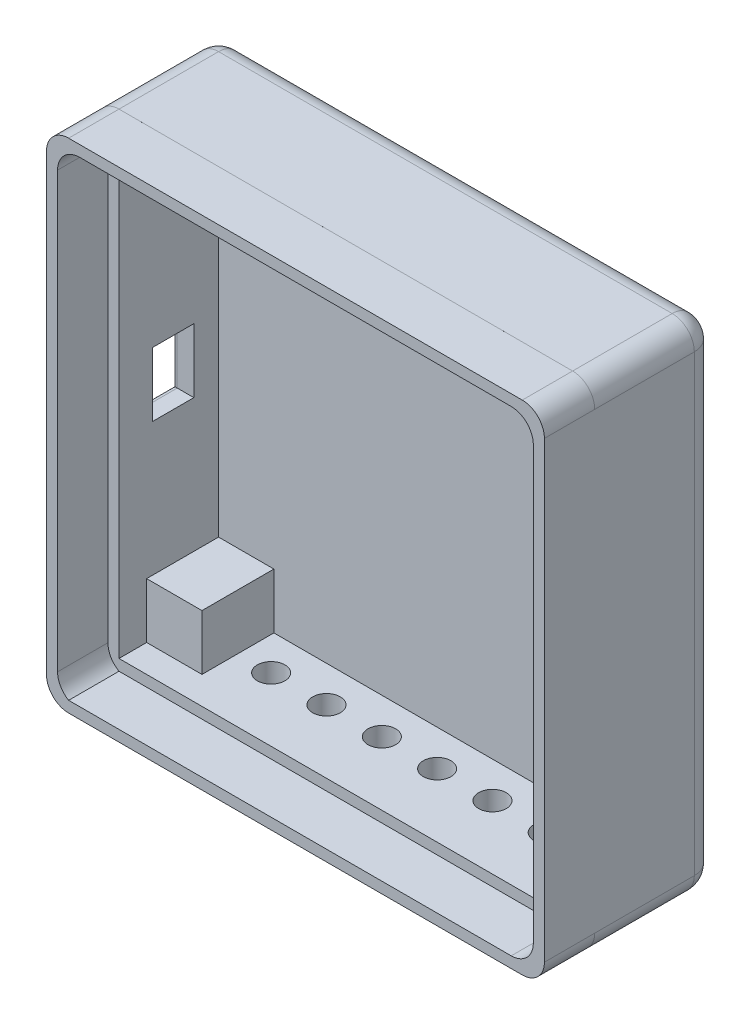
SolidWorks part; units mm, degrees
ref_plane "Piano frontale" through (0, 0, 0) normal (0, 0, 1) x (1, 0, 0)
ref_plane "Piano superiore" through (0, 0, 0) normal (0, 1, 0) x (1, 0, 0)
ref_plane "Piano destro" through (0, 0, 0) normal (1, 0, 0) x (0, 0, -1)
sketch "Schizzo2" plane through (0, 0, 0) normal (0, 0, 1) x (1, 0, 0)
  line L1 (0, 0) -> (45, 0)
  line L2 (0, 0) -> (0, 45)
  line L3 (0, 45) -> (45, 45)
  line L4 (45, 0) -> (45, 45)
  dimension "D1" = 45
  dimension "D2" = 45
extrude "Estrusione-Estrusione2" add sketch "Schizzo2" along normal blind 11
shell "Svuota1" thickness 2 removed face at (22.5, 22.5, 11)
fillet "Raccordo1" radius 2 4 edges at (45, 45, 5.5) (45, 0, 5.5) (0, 0, 5.5) (0, 45, 5.5)
fillet "Raccordo2" radius 2 8 edges at (44.4142, 0.5858, 0) (22.5, 0, 0) (0.5858, 0.5858, 0) (0, 22.5, 0) (0.5858, 44.4142, 0) (22.5, 45, 0) (44.4142, 44.4142, 0) (45, 22.5, 0)
sketch "Schizzo3" plane through (0, 0, 2) normal (0, 0, 1) x (1, 0, 0)
  line L0 (43, 43) -> (2, 43) construction
  line L1 (2, 43) -> (7, 43)
  line L2 (2, 43) -> (2, 38)
  line L3 (2, 38) -> (7, 38)
  line L4 (7, 43) -> (7, 38)
  line L5 (43, 43) -> (2, 43) construction
  dimension "D1" = 5
  dimension "D2" = 5
extrude "Estrusione-Estrusione3" add sketch "Schizzo3" along normal blind 6.5
sketch "Schizzo4" plane through (0, 0, 2) normal (0, 0, 1) x (1, 0, 0)
  line L1 (43, 2) -> (38, 2)
  line L2 (43, 2) -> (43, 7)
  line L3 (43, 7) -> (38, 7)
  line L4 (38, 2) -> (38, 7)
  dimension "D1" = 5
  dimension "D2" = 5
extrude "Estrusione-Estrusione4" add sketch "Schizzo4" along normal blind 6.5
fillet "Raccordo3" radius 4 2 edges at (38, 7, 5.25) (7, 38, 5.25)
sketch "Schizzo5" plane through (0, 0, 2) normal (0, 0, 1) x (1, 0, 0)
  line L0 (43, 2) -> (43, 43) construction
  line L1 (43, 43) -> (38, 43)
  line L2 (43, 43) -> (43, 38)
  line L3 (43, 38) -> (38, 38)
  line L4 (38, 43) -> (38, 38)
  line L5 (43, 43) -> (7, 43) construction
  line L7 (2, 2) -> (7, 2)
  line L8 (2, 2) -> (2, 7)
  line L9 (2, 7) -> (7, 7)
  line L10 (7, 2) -> (7, 7)
  dimension "D1" = 5
  dimension "D2" = 5
  dimension "D3" = 5
  dimension "D4" = 5
extrude "Estrusione-Estrusione5" add sketch "Schizzo5" along normal blind 6.5 contours L2 L1 L4 L3 | L8 L7 L10 L9
sketch "Schizzo7" plane through (0, 0, 0) normal (-1, 0, 0) x (0, 0, 1)
  line L1 (4.2347, 24.8244) -> (7.9559, 24.8244)
  line L2 (4.2347, 24.8244) -> (4.2347, 19.0329)
  line L3 (4.2347, 19.0329) -> (7.9559, 19.0329)
  line L4 (7.9559, 24.8244) -> (7.9559, 19.0329)
extrude "Taglio-Estrusione1" cut sketch "Schizzo7" against normal blind 3
sketch "Schizzo12" plane through (0, 0, 11) normal (0, 0, 1) x (1, 0, 0)
  line L1 (0, 44.9999) -> (45, 44.9999)
  line L2 (0, 44.9999) -> (0, 43.9999)
  line L3 (0, 43.9999) -> (45, 43.9999)
  line L4 (45, 44.9999) -> (45, 43.9999)
  dimension "D1" = 45
  dimension "D2" = 1
extrude "Estrusione-Estrusione7" add sketch "Schizzo12" along normal blind 4.55
sketch "Schizzo13" plane through (0, 0, 11) normal (0, 0, 1) x (1, 0, 0)
  line L1 (45, 43.9999) -> (44, 43.9999)
  line L2 (45, 43.9999) -> (45, -0.0001)
  line L3 (45, -0.0001) -> (44, -0.0001)
  line L4 (44, 43.9999) -> (44, -0.0001)
  dimension "D1" = 44
  dimension "D2" = 1
extrude "Estrusione-Estrusione10" add sketch "Schizzo13" along normal blind 4.55
sketch "Schizzo15" plane through (0, 0, 11) normal (0, 0, 1) x (1, 0, 0)
  line L1 (44, -0.0001) -> (2, -0.0001)
  line L2 (44, -0.0001) -> (44, 0.9999)
  line L3 (44, 0.9999) -> (2, 0.9999)
  line L4 (2, -0.0001) -> (2, 0.9999)
  dimension "D1" = 1
  dimension "D2" = 42
extrude "Estrusione-Estrusione11" add sketch "Schizzo15" along normal blind 4.55
fillet "Raccordo4" radius 2 1 edges at (45, -0.0001, 13.275)
fillet "Raccordo5" radius 2 1 edges at (45, 44.9999, 13.275)
sketch "Schizzo17" plane through (0, 0, 11) normal (0, 0, 1) x (1, 0, 0)
  line L1 (0, 43.9999) -> (1, 43.9999)
  line L2 (0, 43.9999) -> (0, -0.0001)
  line L3 (0, -0.0001) -> (1, -0.0001)
  line L4 (1, 43.9999) -> (1, -0.0001)
  dimension "D1" = 1
  dimension "D2" = 44
extrude "Estrusione-Estrusione13" add sketch "Schizzo17" along normal blind 4.55
fillet "Raccordo6" radius 2 1 edges at (0, 44.9999, 13.275)
fillet "Raccordo7" radius 2 1 edges at (44, 0.9999, 13.275)
fillet "Raccordo8" radius 2 1 edges at (44, 43.9999, 13.275)
fillet "Raccordo9" radius 2 1 edges at (1, 43.9999, 13.275)
sketch "Schizzo18" plane through (0, 0, 11) normal (0, 0, 1) x (1, 0, 0)
  line L0 (1, -0.0001) -> (1, 41.9999) construction
  line L1 (2, -0.0001) -> (1, -0.0001)
  line L2 (2, -0.0001) -> (2, 0.9995)
  line L3 (2, 0.9995) -> (1, 0.9995)
  line L4 (1, -0.0001) -> (1, 0.9995)
extrude "Estrusione-Estrusione14" add sketch "Schizzo18" along normal blind 4.55
fillet "Raccordo10" radius 2 1 edges at (0, -0.0001, 13.275)
fillet "Raccordo11" radius 2 1 edges at (1, 0.9995, 13.275)
fillet "Raccordo12" radius 0.5 4 edges at (0, 19.0329, 6.0953) (0, 21.9286, 7.9559) (0, 21.9286, 4.2347) (0, 24.8244, 6.0953)
sketch "Schizzo21" plane through (0, 2, 0) normal (0, 1, 0) x (1, 0, 0)
  circle A0 centre (10.0012, -5.25) radius 1.25
  circle A1 centre (15.004, -5.25) radius 1.25
  circle A2 centre (20.0048, -5.25) radius 1.25
  circle A3 centre (25.0045, -5.25) radius 1.25
  circle A4 centre (30.0037, -5.25) radius 1.25
  circle A5 centre (35.0006, -5.25) radius 1.25
  dimension "D1" = 2.5
  dimension "D2" = 2.5
  dimension "D3" = 2.5
  dimension "D4" = 2.5
  dimension "D5" = 2.5
  dimension "D6" = 2.5
extrude "Taglio-Estrusione4" cut sketch "Schizzo21" against normal blind 2
